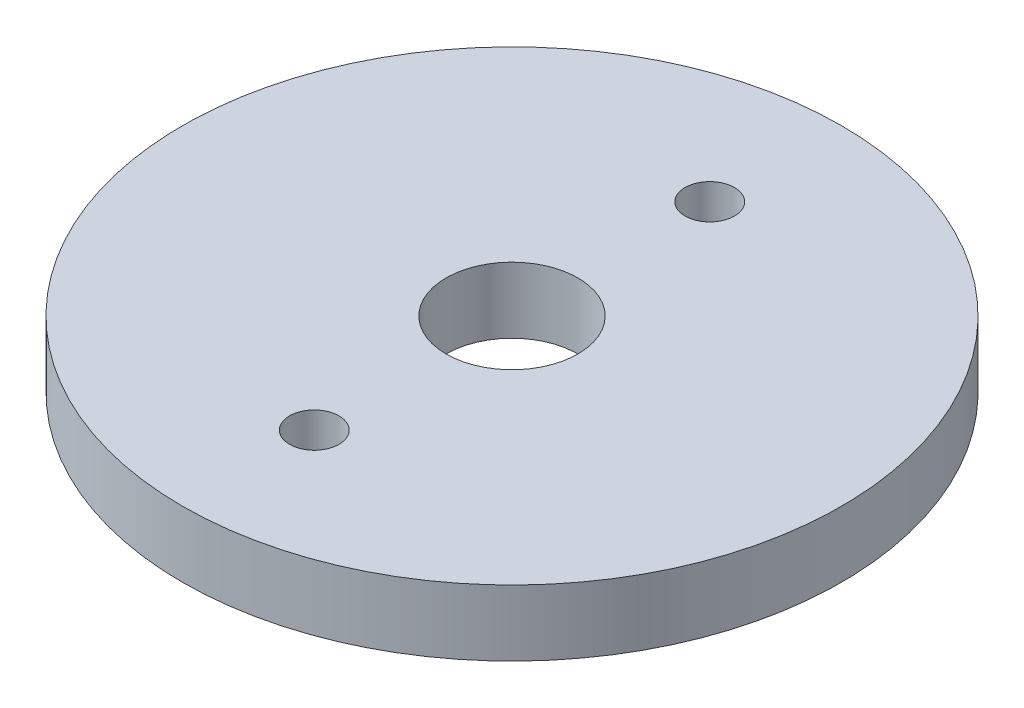
SolidWorks part; units mm, degrees
material "Acrylic (Medium-high impact)"
ref_plane "Front Plane" through (0, 0, 0) normal (0, 0, 1) x (1, 0, 0)
ref_plane "Top Plane" through (0, 0, 0) normal (0, 1, 0) x (1, 0, 0)
ref_plane "Right Plane" through (0, 0, 0) normal (1, 0, 0) x (0, 0, -1)
sketch "Sketch1" plane through (0, 0, 0) normal (0, 1, 0) x (1, 0, 0)
  circle A0 centre (0, 0) radius 20
  dimension "D1" = 40
sketch "Sketch2" plane through (0, 0, 0) normal (0, 1, 0) x (1, 0, 0)
  line L0 (-11.8283, 0) -> (13.8416, 0) construction
  circle A0 centre (0, 0) radius 4
  circle A1 centre (0, 12) radius 1.5
  circle A2 centre (0, -12) radius 1.5
  dimension "D1" = 8
  dimension "D2" = 3
  dimension "D3" = 12
extrude "Boss-Extrude1" add sketch "Sketch1" along normal blind 4
extrude "Cut-Extrude1" cut sketch "Sketch2" along normal up to next
